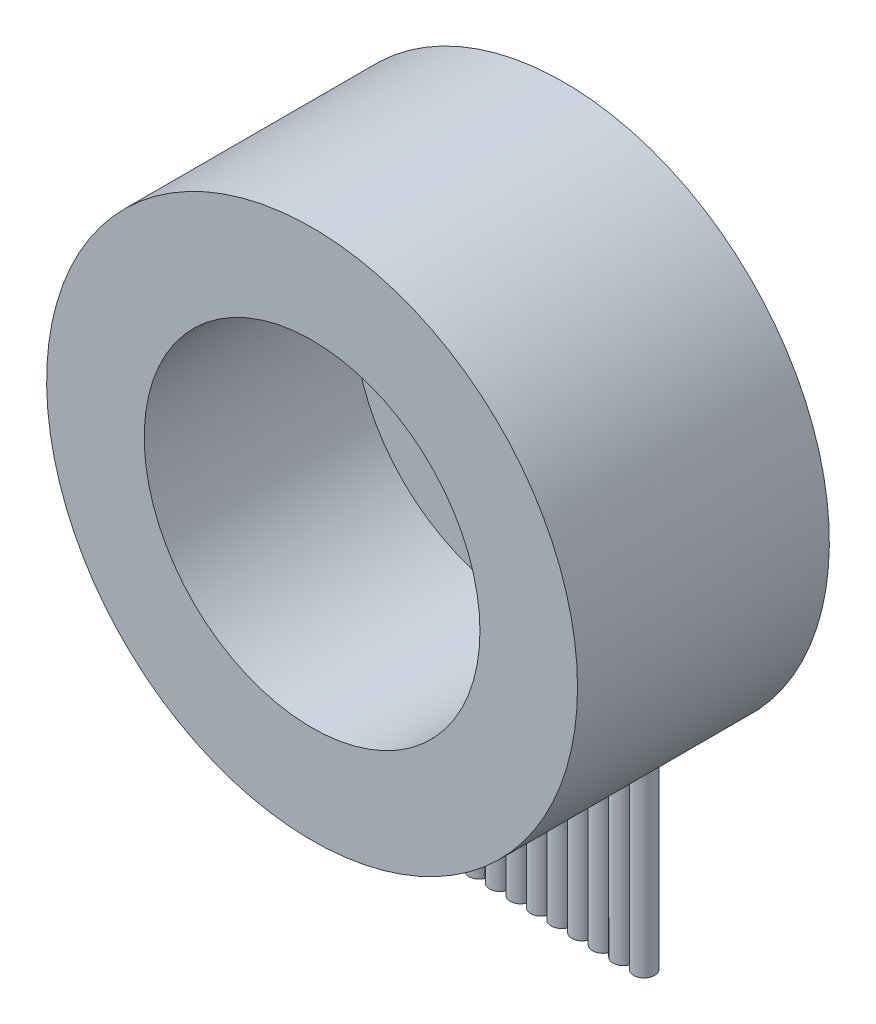
SolidWorks part; units mm, degrees
material "POM 乙缩醛共聚物"
ref_plane "前视基准面" through (0, 0, 0) normal (0, 0, 1) x (1, 0, 0)
ref_plane "上视基准面" through (0, 0, 0) normal (0, 1, 0) x (1, 0, 0)
ref_plane "右视基准面" through (0, 0, 0) normal (1, 0, 0) x (0, 0, -1)
sketch "草图1" plane through (0, 0, 0) normal (0, 0, 1) x (1, 0, 0)
  circle A0 centre (0, 0) radius 12.65
extrude "凸台-拉伸1" add sketch "草图1" along normal blind 12
ref_plane "基准面1" through (0, 0, 1) normal (0, 0, -1) x (-1, 0, 0)
sketch "草图2" plane through (0, 0, 1) normal (0, 0, -1) x (-1, 0, 0)
  line L0 (0, -12.65) -> (0, -1.837) construction
  line L1 (0, -11.3795) -> (-5.5253, -11.3795)
  line L2 (0, -11.3795) -> (5.5253, -11.3795)
  circle A0 centre (0, 0) radius 12.65 construction
  arc A1 (-5.5253, -11.3795) -> (5.5253, -11.3795) centre (0, 0) ccw
extrude "切除-拉伸1" cut sketch "草图2" along normal blind 9
extrude "切除-拉伸2" cut sketch "草图2<2>" against normal blind 0.5
sketch "草图2<2>" plane through (0, 0, 1) normal (0, 0, -1) x (-1, 0, 0) same geometry as "草图2"
sketch "草图3" plane through (0, -11.3795, 0) normal (0, -1, 0) x (1, 0, 0)
  line L0 (-13.2162, 1) -> (13.2162, 1) construction
  line L1 (-4.0526, 0.7233) -> (-3.9567, 0.7233)
  line L3 (4.0885, 0.3929) -> (3.9244, 0.3929)
  line L4 (-3.0433, 0.7233) -> (-2.9649, 0.7233)
  line L5 (-3.9837, 0.3929) -> (-4.0116, 0.3929)
  line L6 (-2.0351, 0.7233) -> (-1.9722, 0.7233)
  line L7 (-2.9781, 0.3929) -> (-3.0163, 0.3929)
  line L8 (-1.0278, 0.7233) -> (-0.9786, 0.7233)
  line L9 (-1.9716, 0.3929) -> (-2.0219, 0.3929)
  line L10 (-0.0214, 0.7233) -> (0.0159, 0.7233)
  line L11 (-0.9642, 0.3929) -> (-1.0284, 0.3929)
  line L12 (0.9841, 0.7233) -> (1.0112, 0.7233)
  line L13 (0.0441, 0.3929) -> (-0.0358, 0.3929)
  line L14 (1.9888, 0.7233) -> (2.0074, 0.7233)
  line L15 (1.0535, 0.3929) -> (0.9559, 0.3929)
  line L16 (2.9926, 0.7233) -> (3.0044, 0.7233)
  line L17 (2.064, 0.3929) -> (1.9465, 0.3929)
  line L18 (3.9956, 0.7233) -> (4.0022, 0.7233)
  line L19 (3.0756, 0.3929) -> (2.936, 0.3929)
  arc A0 (-4.0526, 0.7233) -> (-4.0116, 0.3929) centre (-4.5, 0.5) ccw
  arc A1 (-3.9837, 0.3929) -> (-3.0163, 0.3929) centre (-3.5, 0.5196) ccw
  arc A2 (-2.9781, 0.3929) -> (-2.0219, 0.3929) centre (-2.5, 0.5393) ccw
  arc A3 (-1.9716, 0.3929) -> (-1.0284, 0.3929) centre (-1.5, 0.5589) ccw
  arc A4 (-0.9642, 0.3929) -> (-0.0358, 0.3929) centre (-0.5, 0.5786) ccw
  arc A5 (0.0441, 0.3929) -> (0.9559, 0.3929) centre (0.5, 0.5982) ccw
  arc A6 (1.0535, 0.3929) -> (1.9465, 0.3929) centre (1.5, 0.6179) ccw
  arc A7 (2.064, 0.3929) -> (2.936, 0.3929) centre (2.5, 0.6375) ccw
  arc A8 (3.0756, 0.3929) -> (3.9244, 0.3929) centre (3.5, 0.6572) ccw
  arc A9 (4.0885, 0.3929) -> (4.0022, 0.7233) centre (4.5, 0.6768) ccw
  arc A10 (-3.0433, 0.7233) -> (-3.9567, 0.7233) centre (-3.5, 0.5196) ccw
  arc A11 (-2.0351, 0.7233) -> (-2.9649, 0.7233) centre (-2.5, 0.5393) ccw
  arc A12 (-1.0278, 0.7233) -> (-1.9722, 0.7233) centre (-1.5, 0.5589) ccw
  arc A13 (-0.0214, 0.7233) -> (-0.9786, 0.7233) centre (-0.5, 0.5786) ccw
  arc A14 (0.9841, 0.7233) -> (0.0159, 0.7233) centre (0.5, 0.5982) ccw
  arc A15 (1.9888, 0.7233) -> (1.0112, 0.7233) centre (1.5, 0.6179) ccw
  arc A16 (2.9926, 0.7233) -> (2.0074, 0.7233) centre (2.5, 0.6375) ccw
  arc A17 (3.9956, 0.7233) -> (3.0044, 0.7233) centre (3.5, 0.6572) ccw
  dimension "D1" = 10
extrude "凸台-拉伸5" add sketch "草图3" along normal blind 10
sketch "草图4" plane through (0, 0, 12) normal (0, 0, 1) x (1, 0, 0)
  circle A0 centre (0, 0) radius 8
extrude "切除-拉伸3" cut sketch "草图4" against normal blind 10
sketch "草图5" plane through (0, 0, 0) normal (0, 0, -1) x (-1, 0, 0)
  line L0 (-4.7115, -10.8124) -> (4.7115, -10.8124)
  line L1 (-4.7103, -10.8152) -> (4.7103, -10.8152)
  arc A0 (4.7103, -10.8152) -> (-4.7103, -10.8152) centre (0, 0) ccw
  arc A1 (4.7115, -10.8124) -> (-4.7115, -10.8124) centre (0, 0) ccw
extrude "切除-拉伸4" cut sketch "草图5" against normal blind 1
